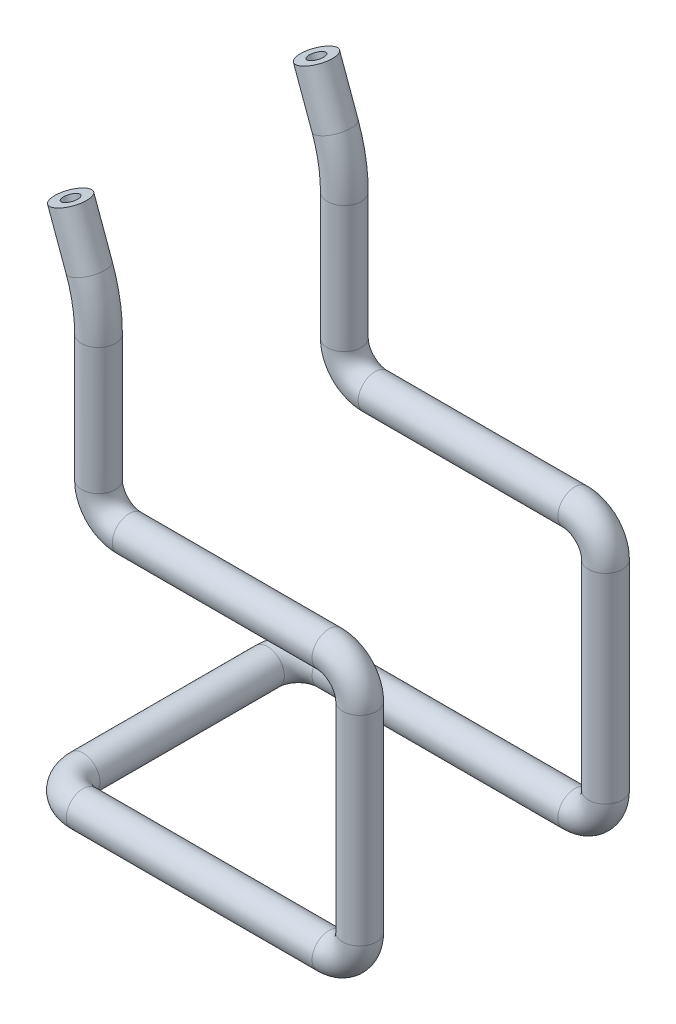
SolidWorks part; units mm, degrees
ref_plane "Front Plane" through (0, 0, 0) normal (0, 0, 1) x (1, 0, 0)
ref_plane "Top Plane" through (0, 0, 0) normal (0, 1, 0) x (1, 0, 0)
ref_plane "Right Plane" through (0, 0, 0) normal (1, 0, 0) x (0, 0, -1)
sketch3d "3DSketch3"
  line L0 (0, 0, 0) -> (0, 0, -30)
  line L1 (10, 0, -40) -> (90, 0, -40)
  line L2 (100, 10, -40) -> (100, 75, -40)
  line L3 (90, 85, -40) -> (25, 85, -40)
  line L4 (15, 95, -40) -> (15, 136.1781, -40)
  line L5 (11.9846, 153.2791, -40) -> (5.9365, 169.8963, -40)
  arc A0 (15, 136.1781, -40) -> (11.9846, 153.2791, -40) centre (-35, 136.1781, -40) ccw
  arc A1 (0, 0, -30) -> (10, 0, -40) centre (10, 0, -30) ccw
  arc A2 (25, 85, -40) -> (15, 95, -40) centre (25, 95, -40) ccw
  arc A3 (90, 0, -40) -> (100, 10, -40) centre (90, 10, -40) ccw
  arc A4 (100, 75, -40) -> (90, 85, -40) centre (90, 75, -40) ccw
  point P8 (0, 0, 0)
  point P9 (9.1084, 169.616, -33.1126)
  point P10 (17.0166, 168.9152, -48.8363)
  point P11 (8.2447, 169.6924, -33.9573)
  point P14 (15, 144.9945, -40)
  point P15 (-35, 136.1781, 10)
  point P18 (0, 0, -40)
  point P19 (10, -10, -30)
  point P22 (15, 85, -40)
  point P23 (25, 95, -50)
  point P26 (100, 0, -40)
  point P27 (90, 10, -30)
  point P30 (100, 85, -40)
  point P31 (90, 75, -30)
  dimension "D8" = 50
  dimension "D9" = 10
  dimension "D1" = 40
  dimension "D2" = 100
  dimension "D3" = 85
  dimension "D4" = 85
  dimension "D5" = 26.5
  dimension "D6" = 20
  dimension "D7" = 170
sweep "Sweep-Thin1" add path "3DSketch3" circular profile diameter 5 parameters "D1"=3, "D3"=5
mirror "Mirror1" about plane through (0, 0, 0) normal (0, 0, 1) of "Sweep-Thin1"
